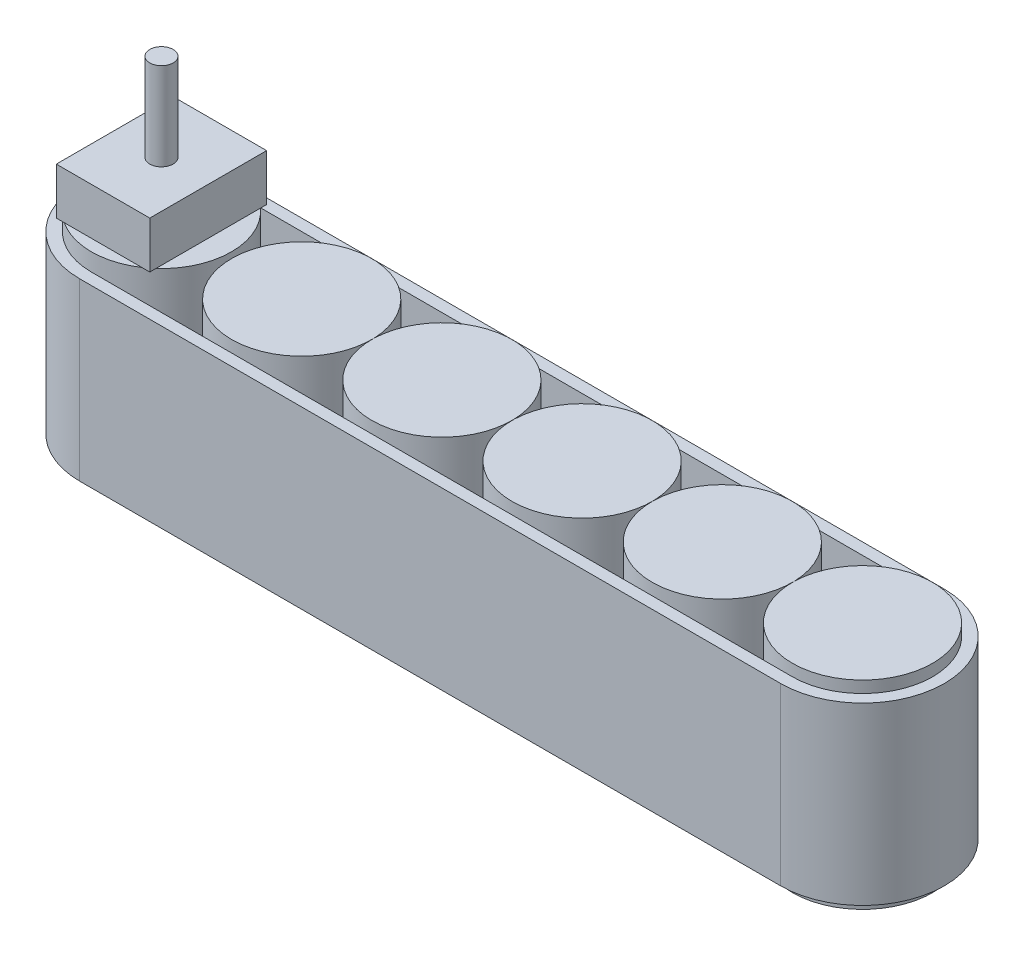
SolidWorks part; units mm, degrees
ref_plane "Front Plane" through (0, 0, 0) normal (0, 0, 1) x (1, 0, 0)
ref_plane "Top Plane" through (0, 0, 0) normal (0, 1, 0) x (1, 0, 0)
ref_plane "Right Plane" through (0, 0, 0) normal (1, 0, 0) x (0, 0, -1)
sketch "Sketch1" plane through (0, 0, 0) normal (0, 1, 0) x (1, 0, 0)
  line L0 (0, 0) -> (600, 0) construction
  line L1 (0, 60) -> (600, 60)
  line L2 (0, -60) -> (600, -60)
  line L3 (0, 70) -> (600, 70)
  line L4 (0, -70) -> (600, -70)
  arc A0 (0, 60) -> (0, -60) centre (0, 0) ccw
  arc A1 (600, -60) -> (600, 60) centre (600, 0) ccw
  arc A2 (600, -70) -> (600, 70) centre (600, 0) ccw
  arc A3 (0, 70) -> (0, -70) centre (0, 0) ccw
  point P3 (300, 0)
  dimension "D2" = 60
  dimension "D1" = 600
  dimension "D3" = 10
extrude "Boss-Extrude1" add sketch "Sketch1" along normal mid plane 150
sketch "Sketch3" plane through (0, 0, 0) normal (0, 1, 0) x (1, 0, 0)
  circle A0 centre (0, 0) radius 60
  arc A1 (0, 60) -> (0, -60) centre (0, 0) ccw construction
  circle A2 centre (120, 0) radius 60
  circle A3 centre (240, 0) radius 60
  circle A4 centre (360, 0) radius 60
  circle A5 centre (480, 0) radius 60
  circle A6 centre (600, 0) radius 60
  point P7 (0, 0)
  point P17 (121.9569, 0)
  dimension "D1" = 6
extrude "Boss-Extrude2" add sketch "Sketch3" along normal mid plane 170 contours A0 | A2 | A3 | A4 | A5 | A6 region at (0, 0, 0) region at (600, 0, 0) region at (480, 0, 0) region at (360, 0, 0) region at (240, 0, 0) region at (120, 0, 0)
sketch "Sketch4" plane through (0, -85, 0) normal (0, -1, 0) x (1, 0, 0)
  circle A0 centre (0, 0) radius 12.5
  dimension "D1" = 25
extrude "Boss-Extrude3" add sketch "Sketch4" along normal blind 40
sketch "Sketch5" plane through (0, 85, 0) normal (0, 1, 0) x (1, 0, 0)
  circle A0 centre (0, 0) radius 10
  dimension "D1" = 20
extrude "Boss-Extrude4" add sketch "Sketch5" along normal blind 120
sketch "Sketch6" plane through (0, 85, 0) normal (0, 1, 0) x (1, 0, 0)
  circle A1 centre (0, 0) radius 60
  circle A2 centre (0, 0) radius 60
  dimension "D1" = 0
extrude "Boss-Extrude7" add sketch "Sketch6" along normal blind 5
sketch "Sketch7" plane through (0, 90, 0) normal (0, 1, 0) x (1, 0, 0)
  line L1 (-40, 50) -> (40, 50)
  line L2 (-40, 50) -> (-40, -50)
  line L3 (-40, -50) -> (40, -50)
  line L4 (40, 50) -> (40, -50)
  line L5 (-40, 50) -> (40, -50) construction
  line L6 (-40, -50) -> (40, 50) construction
  circle A0 centre (0, 0) radius 10 construction
  circle A1 centre (0, 0) radius 10
  point P0 (0, 0)
  dimension "D1" = 100
  dimension "D2" = 80
extrude "Boss-Extrude8" add sketch "Sketch7" along normal blind 40
